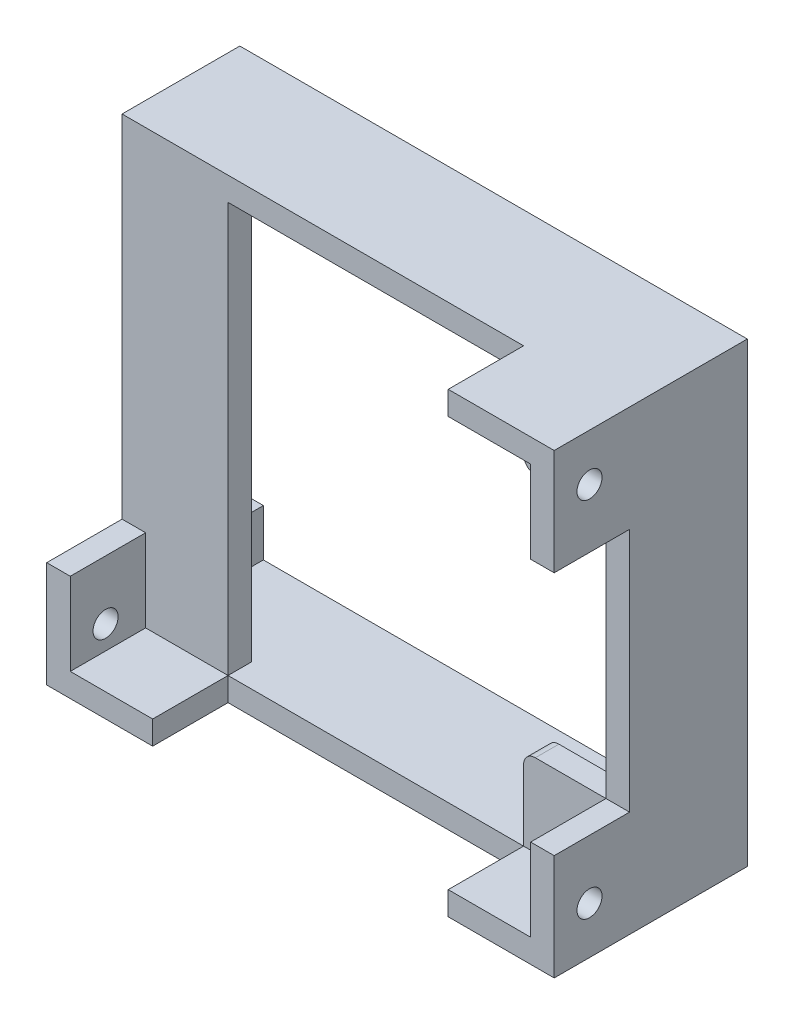
SolidWorks part; units mm, degrees
ref_plane "Front Plane" through (0, 0, 0) normal (0, 0, 1) x (1, 0, 0)
ref_plane "Top Plane" through (0, 0, 0) normal (0, 1, 0) x (1, 0, 0)
ref_plane "Right Plane" through (0, 0, 0) normal (1, 0, 0) x (0, 0, -1)
ref_axis "X-Axis" through (-88.99, 0, 0) along (1, 0, 0)
ref_axis "Y-Axis" through (0, 55, 0) along (0, -1, 0)
ref_axis "Z-Axis" through (0, 0, -88.99) along (0, 0, 1)
sketch "Sketch1" plane through (0, 0, 0) normal (0, 0, 1) x (1, 0, 0)
  line L0 (0, 0) -> (39.1, 0)
  line L1 (39.1, 0) -> (39.1, -34.8)
  line L2 (0, 0) -> (0, -5)
  line L3 (39.1, -34.8) -> (34.1, -34.8)
  line L4 (0, -5) -> (0, -34.8)
  line L5 (0, -34.8) -> (34.1, -34.8)
  dimension "D1" = 34.8
  dimension "39.6" = 39.1
  dimension "D2" = 5
  dimension "D3" = 5
extrude "Extrude-Thin1" add sketch "Sketch1" against normal blind 10 thin thin type one direction wall 2
sketch "Sketch2" plane through (0, 0, 0) normal (0, 0, 1) x (1, 0, 0)
  line L0 (7, -7) -> (7, -34.8) construction
  line L1 (0, 0) -> (7, 0)
  line L2 (0, 0) -> (0, -7)
  line L3 (0, -7) -> (7, -7)
  line L4 (7, 0) -> (7, -7)
  line L5 (39.1, 0) -> (32.1, 0)
  line L6 (39.1, 0) -> (39.1, -7)
  line L7 (39.1, -7) -> (32.1, -7)
  line L8 (32.1, 0) -> (32.1, -7)
  line L13 (39.1, -34.8) -> (32.1, -34.8)
  line L14 (39.1, -34.8) -> (39.1, -27.8)
  line L15 (39.1, -27.8) -> (32.1, -27.8)
  line L16 (32.1, -34.8) -> (32.1, -27.8)
  line L17 (0, -34.8) -> (39.1, -34.8) construction
  line L18 (0, -27.8) -> (7, -27.8)
  line L19 (32.1, -27.8) -> (0, -27.8) construction
  line L20 (0, 0) -> (0, -34.8) construction
  line L21 (7, -27.8) -> (7, -34.8)
  line L22 (7, -34.8) -> (0, -34.8)
  line L23 (0, -34.8) -> (0, -27.8)
  dimension "D1" = 7
  dimension "D2" = 7
  dimension "D3" = 7
  dimension "D4" = 7
  dimension "D5" = 7
  dimension "D6" = 7
extrude "Boss-Extrude1" add sketch "Sketch2" against normal blind 2
fillet "Fillet1" radius 1 4 edges at (32.1, -7, -1) (32.1, -27.8, -1) (7, -7, -1) (7, -27.8, -1)
mirror "Mirror1" about plane through (39.1, 0, -10) normal (1, 0, 0) of bodies 102
delete or keep bodies "Body-Delete/Keep 1" type delete bodies bodies 102
sketch "Sketch3" plane through (37.1, 0, 0) normal (-1, 0, 0) x (0, 0, 1)
  line L0 (-10, -36.8) -> (-10, 2) construction
  line L1 (-10, -2) -> (0, -2)
  line L2 (-10, -2) -> (-10, -30.8)
  line L3 (-10, -30.8) -> (0, -30.8)
  line L4 (0, -2) -> (0, -30.8)
  line L5 (-10, 2) -> (-10, -2) construction
  line L6 (-10, -30.8) -> (-10, -34.8) construction
  line L7 (0, -36.8) -> (0, 2) construction
  dimension "D1" = 4
  dimension "D2" = 0
extrude "Cut-Extrude1" cut sketch "Sketch3" against normal up to next
sketch "Sketch4" plane through (0, 0, 0) normal (0, 0, 1) x (1, 0, 0)
  line L1 (37.1, -30.8) -> (46.1, -30.8)
  line L2 (37.1, -30.8) -> (37.1, -2)
  line L3 (37.1, -2) -> (46.1, -2)
  line L4 (46.1, -30.8) -> (46.1, -2)
extrude "Boss-Extrude2" add sketch "Sketch4" against normal up to surface (2 mm away) up to face at (42.6, -32.8, -2)
sketch "Sketch5" plane through (0, 0, 0) normal (0, 0, 1) x (1, 0, 0)
  line L0 (71.2, -34.8) -> (71.2, -36.8)
  line L1 (80.2, -36.8) -> (37.1, -36.8) construction
  line L2 (71.2, -36.8) -> (80.2, -36.8)
  line L3 (80.2, -36.8) -> (80.2, -27.8)
  line L6 (78.2, -27.8) -> (80.2, -27.8)
  line L7 (71.2, -34.8) -> (78.2, -34.8)
  line L8 (78.2, -34.8) -> (78.2, -27.8)
extrude "Boss-Extrude3" add sketch "Sketch5" along normal blind 6.4
ref_plane "Plane1" through (58.65, 0, 0) normal (1, 0, 0) x (0, 0, -1)
ref_plane "Plane2" through (0, -17.4, 0) normal (0, 1, 0) x (1, 0, 0)
mirror "Mirror2" about plane through (0, -17.4, 0) normal (0, 1, 0) of "Boss-Extrude3"
mirror "Mirror3" about plane through (58.65, 0, 0) normal (1, 0, 0) of "Boss-Extrude3"
sketch "Sketch6" plane through (80.2, 0, 0) normal (1, 0, 0) x (0, 0, -1)
  line L0 (10, -36.8) -> (-6.4, -36.8) construction
  line L1 (-6.4, -36.8) -> (-6.4, -27.8) construction
  circle A0 centre (-3.4, -32.8) radius 1.065
  point P6 (-5.2425, -34.7094)
  dimension "D3" = 2.13
  dimension "D1" = 4
  dimension "D2" = 3
extrude "Cut-Extrude2" cut sketch "Sketch6" against normal through all
mirror "Mirror4" about plane through (0, -17.4, 0) normal (0, 1, 0) of "Cut-Extrude2"
